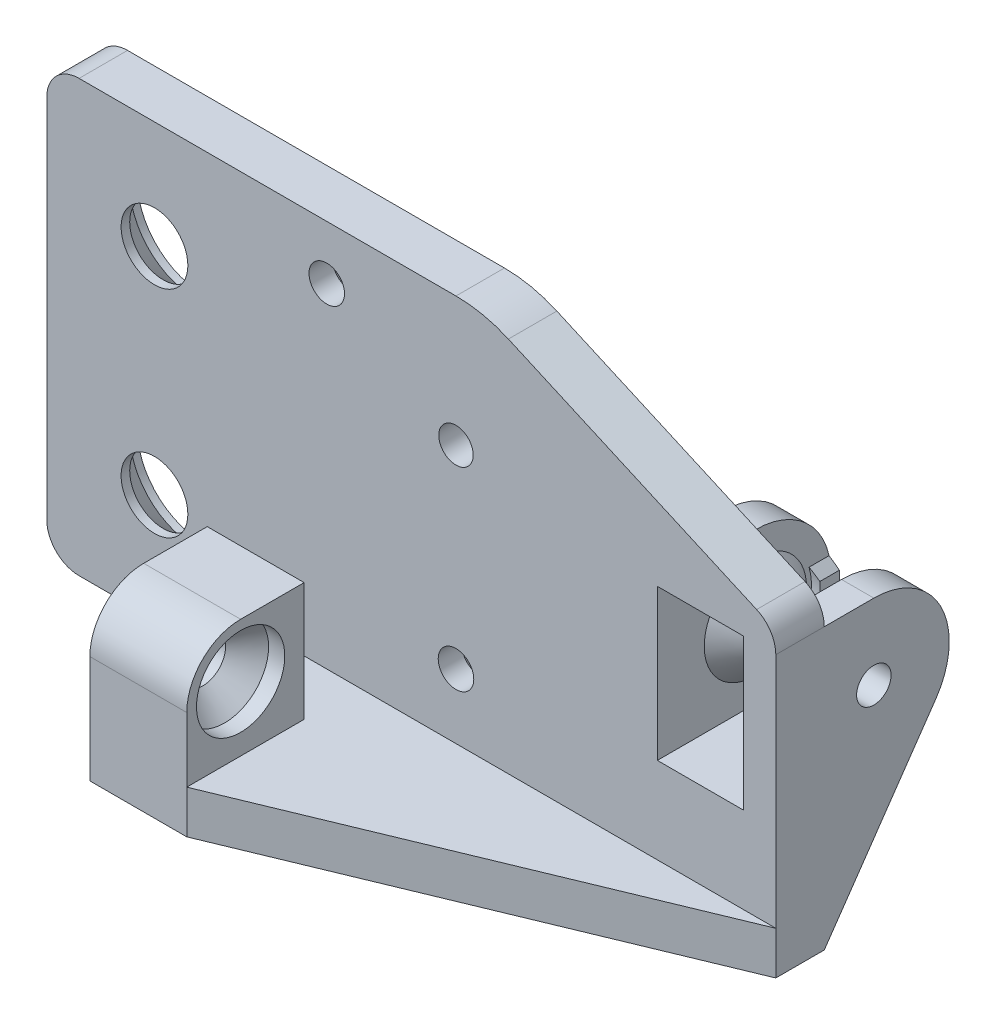
SolidWorks part; units mm, degrees
material "Custom Plastic"
ref_plane "Front Plane" through (0, 0, 0) normal (0, 0, 1) x (1, 0, 0)
ref_plane "Top Plane" through (0, 0, 0) normal (0, 1, 0) x (1, 0, 0)
ref_plane "Right Plane" through (0, 0, 0) normal (1, 0, 0) x (0, 0, -1)
sketch "Sketch1" plane through (0, 0, 0) normal (0, 0, 1) x (1, 0, 0)
  line L0 (-10, -20) -> (-10, 0) construction
  line L1 (-10, -20) -> (10, -20) construction
  line L2 (-10, 0) -> (10, 0) construction
  line L3 (10, -20) -> (10, 0) construction
  line L4 (-10, -20) -> (10, 0) construction
  line L5 (-10, 0) -> (10, -20) construction
  line L6 (-10, 0) -> (-10, 20) construction
  line L7 (-10, 17) -> (-10, -17)
  line L8 (-10, 20) -> (10, 20) construction
  line L9 (10, 0) -> (10, 20) construction
  line L10 (-10, 0) -> (10, 20) construction
  line L11 (-10, 20) -> (10, 0) construction
  line L12 (-7, 20) -> (10, 20)
  line L13 (57.7, 20) -> (57.7, -20)
  line L15 (10, 20) -> (57.7, 20)
  line L18 (57.7, -20) -> (-7, -20)
  circle A0 centre (0, 10) radius 3.1
  circle A1 centre (0, -10) radius 3.1
  arc A2 (-7, 20) -> (-10, 17) centre (-7, 17) ccw
  arc A3 (-10, -17) -> (-7, -20) centre (-7, -17) ccw
  circle A4 centre (28, 8) radius 1.6
  point P0 (0, 10)
  point P1 (0, -10)
  dimension "D2" = 6.2
  dimension "D6" = 3
  dimension "D4" = 3.2
  dimension "D1" = 20
  dimension "D3" = 57.7
  dimension "D5" = 18
  dimension "D7" = 8
extrude "Boss-Extrude1" add sketch "Sketch1" along normal blind 4.5
sketch "Sketch2" plane through (0, -20, 0) normal (0, -1, 0) x (1, 0, 0)
  line L0 (10, 4.5) -> (10, 20.5)
  line L1 (-7, 4.5) -> (57.7, 4.5) construction
  line L2 (10, 20.5) -> (19, 20.5)
  line L3 (19, 20.5) -> (57.7, 4.5)
  line L4 (57.7, 4.5) -> (10, 4.5)
  dimension "D1" = 16
  dimension "D2" = 10
  dimension "D3" = 9
extrude "Boss-Extrude2" add sketch "Sketch2" against normal blind 15
sketch "Sketch3" plane through (57.7, 0, 0) normal (1, 0, 0) x (0, 0, -1)
  line L0 (4.6036, 6) -> (0, 6)
  line L1 (0, -20) -> (0, 20) construction
  line L2 (0, 6) -> (0, -20)
  line L4 (0, -20) -> (10.3655, -4.975)
  arc A0 (10.3655, -4.975) -> (4.6036, 6) centre (4.6036, -1) ccw
  dimension "D1" = 7
  dimension "D2" = 1
extrude "Boss-Extrude3" add sketch "Sketch3" against normal blind 14
sketch "Sketch4" plane through (0, -5, 0) normal (0, 1, 0) x (1, 0, 0)
  line L0 (57.7, -4.5) -> (57.7, 0) construction
  line L1 (10, -4.5) -> (57.7, -4.5)
  line L2 (10, -4.5) -> (10, -9.6)
  line L3 (10, -9.6) -> (19, -9.6)
  line L4 (57.7, -4.5) -> (57.7, -20.5)
  line L5 (19, -20.5) -> (19, -9.6)
  line L6 (19, -20.5) -> (57.7, -20.5)
  dimension "D1" = 5.1
extrude "Cut-Extrude1" cut sketch "Sketch4" against normal offset from surface (11 mm away) 4 contours L6 L4 L1 L2 L3 L5 up to face at (17.9063, -20, 7.8125)
sketch "Sketch5" plane through (57.7, 0, 0) normal (1, 0, 0) x (0, 0, -1)
  circle A0 centre (4.6036, -1) radius 1.6
  dimension "D1" = 3.2
extrude "Cut-Extrude2" cut sketch "Sketch5" against normal through all
sketch "Sketch6" plane through (57.7, 0, 0) normal (1, 0, 0) x (0, 0, -1)
  line L0 (0.7145, 2.8891) -> (8.8191, 10.9937)
  line L1 (8.8191, 10.9937) -> (8.8191, -12.9937)
  line L2 (8.8191, -12.9937) -> (0.7145, -4.8891)
  arc A0 (0.7145, 2.8891) -> (0.7145, -4.8891) centre (4.6036, -1) ccw
  dimension "D1" = 5.5
extrude "Cut-Extrude3" cut sketch "Sketch6" against normal blind 8 from offset 3 offset against normal yes
fillet "Fillet1" radius 5 1 edges at (14.5, -5, 20.5)
sketch "Sketch7" plane through (19, 0, 0) normal (1, 0, 0) x (0, 0, -1)
  line L0 (-4.5, -20) -> (-20.5, -20) construction
  line L1 (-20.5, -10) -> (-20.5, -16) construction
  circle A0 centre (-15.5, -10) radius 2.1
  dimension "D1" = 4.2
  dimension "D2" = 10
  dimension "D3" = 5
extrude "Cut-Extrude4" cut sketch "Sketch7" against normal through all
sketch "Sketch8" plane through (19, 0, 0) normal (1, 0, 0) x (0, 0, -1)
  circle A0 centre (-15.5, -10) radius 4.1
  dimension "D1" = 8.2
extrude "Cut-Extrude5" cut sketch "Sketch8" against normal offset from surface (1.5 mm away) 7.5 up to face at (10, -12.1, 15.5)
chamfer "Chamfer1" distance 2 angle 45 1 edges at (17.5, -12.1, 15.5)
ref_axis "Axis1" through (54.7, -1, -4.6036) along (1, 0, 0)
sketch "Sketch9" plane through (0, 0, 4.5) normal (0, 0, 1) x (1, 0, 0)
  line L0 (46.7, -4.8891) -> (46.7, 2.8891) construction
  line L1 (46.7, 6) -> (54.7, 6)
  line L2 (46.7, 6) -> (46.7, 3.5)
  line L3 (46.7, 3.5) -> (54.7, 3.5) construction
  line L4 (54.7, 6) -> (54.7, 3.5)
  line L5 (54.7, 2.8891) -> (54.7, -4.8891) construction
  line L6 (54.7, -4.8891) -> (54.7, -10.6352) construction
  line L7 (46.7, -5.5) -> (54.7, -5.5) construction
  line L8 (46.7, -5.5) -> (46.7, -8)
  line L9 (46.7, -8) -> (54.7, -8)
  line L10 (54.7, -5.5) -> (54.7, -8)
  line L11 (54.7, 3.5) -> (54.7, -5.5)
  line L12 (54.7, -1) -> (57.7, -1) construction
  line L13 (46.7, 3.5) -> (46.7, -5.5)
  point P14 (54.7, -1)
  dimension "D1" = 2.5
  dimension "D2" = 9
extrude "Cut-Extrude6" cut sketch "Sketch9" against normal through all
sketch "Sketch10" plane through (0, 0, 0) normal (0, 0, -1) x (-1, 0, 0)
  line L1 (-57.7, 6) -> (-57.7, 20)
  line L2 (-57.7, 20) -> (-28, 20)
  line L3 (-55.9166, 8.7422) -> (-32.8666, 18.9689)
  arc A0 (-28, 20) -> (-32.8666, 18.9689) centre (-28, 8) ccw
  arc A1 (-55.9166, 8.7422) -> (-57.7, 6) centre (-54.7, 6) ccw
extrude "Cut-Extrude7" cut sketch "Sketch10" against normal through all
sketch "Sketch11" plane through (0, 0, 0) normal (0, 0, -1) x (-1, 0, 0)
  line L1 (-30.75, -8.4123) -> (-30.75, -11.5877) construction
  line L2 (-30.75, -11.5877) -> (-28, -13.1754) construction
  line L3 (-28, -13.1754) -> (-25.25, -11.5877) construction
  line L4 (-25.25, -11.5877) -> (-25.25, -8.4123) construction
  line L5 (-25.25, -8.4123) -> (-28, -6.8246) construction
  line L6 (-28, -6.8246) -> (-30.75, -8.4123) construction
  line L7 (-13.25, 13.4123) -> (-13.25, 16.5877) construction
  line L8 (-13.25, 16.5877) -> (-16, 18.1754) construction
  line L9 (-16, 18.1754) -> (-18.75, 16.5877) construction
  line L10 (-18.75, 16.5877) -> (-18.75, 13.4123) construction
  line L11 (-18.75, 13.4123) -> (-16, 11.8246) construction
  line L12 (-16, 11.8246) -> (-13.25, 13.4123) construction
  circle A0 centre (-16, 15) radius 1.65
  circle A1 centre (-28, -10) radius 1.65
  circle A2 centre (-28, -10) radius 2.75 construction
  circle A3 centre (-16, 15) radius 2.75 construction
  circle A4 centre (-28, 8) radius 1.6 construction
  point P20 (-28, 8)
  dimension "D1" = 3.3
  dimension "D2" = 5.5
  dimension "D6" = 10
  dimension "D3" = 12
  dimension "D4" = 15
extrude "Cut-Extrude9" cut sketch "Sketch11" against normal through all
sketch "Sketch13" plane through (46.7, 0, 0) normal (1, 0, 0) x (0, 0, -1)
  circle A0 centre (4.6036, -1) radius 2.75
  circle A1 centre (4.6036, -1) radius 1.6
  circle A4 centre (4.6036, -1) radius 1.6 construction
  point P9 (4.6036, -2.5)
  point P11 (10.6036, -2.5)
  point P12 (4.6036, 0.5)
  point P13 (10.6036, 0.5)
  dimension "D1" = 5.5
extrude "Boss-Extrude4" add sketch "Sketch13" along normal blind 2
sketch "Sketch15" plane through (46.7, 0, 0) normal (1, 0, 0) x (0, 0, -1)
  line L1 (9.5826, 0.5) -> (11.441, 0.5)
  line L3 (9.5826, -2.5) -> (11.441, -2.5)
  arc A0 (9.5826, -2.5) -> (9.5826, 0.5) centre (4.6036, -1) ccw
  arc A1 (11.441, -2.5) -> (11.441, 0.5) centre (4.6036, -1) ccw
  arc A2 (10.3655, -4.975) -> (4.6036, 6) centre (4.6036, -1) ccw construction
  dimension "D1" = 5.2
  dimension "D2" = 3
extrude "Boss-Extrude5" add sketch "Sketch15" along normal blind 0.825
ref_plane "Plane1" through (50.7, 0, 0) normal (1, 0, 0) x (0, 0, -1)
mirror "Mirror1" about plane through (50.7, 0, 0) normal (1, 0, 0) of "Boss-Extrude5", "Boss-Extrude4"
chamfer "Chamfer3" distance 2 angle 45 2 edges at (54.7, 1.75, -4.6036) (46.7, 1.75, -4.6036)
sketch "Sketch14" plane through (0, 0, 0) normal (0, 0, -1) x (-1, 0, 0)
  circle A0 centre (0, -10) radius 6.1
  circle A1 centre (0, 10) radius 6.1
  dimension "D1" = 12.2
extrude "Cut-Extrude10" cut sketch "Sketch14" against normal blind 0.7
chamfer "Chamfer4" distance 3 angle 45 2 edges at (-3.1, -10, 0.7) (-3.1, 10, 0.7)
chamfer "Chamfer5" distance 0.83 angle 45 4 edges at (53.875, -2.5, -10.5118) (53.875, 0.5, -10.5118) (47.525, -2.5, -10.5118) (47.525, 0.5, -10.5118)
sketch "Sketch16" plane through (0, 0, 0) normal (0, 0, -1) x (-1, 0, 0)
  circle A0 centre (-28, -10) radius 3.4
  circle A1 centre (-16, 15) radius 3.4
  dimension "D1" = 6.8
extrude "Cut-Extrude11" cut sketch "Sketch16" against normal blind 0.5
chamfer "Chamfer6" distance 1.8 angle 45 2 edges at (26.35, -10, 0.5) (14.35, 15, 0.5)
equation "\"y-cross-rib-thickness\"=4"
equation "\"y-rib-thickness\"=6"
equation "\"bed-plate-thickness\"=3"
equation "\"x-plate-thickness\"=5"
equation "\"rod-diameter\"=12"
equation "\"t-nut-hole-diameter\"=3"
equation "\"y-plate-thickness\"=5"
equation "\"D1@Sketch4\"=\"y-plate-thickness\"+.1"
equation "\"D1@Boss-Extrude5\"=(8-6.35)/2"
